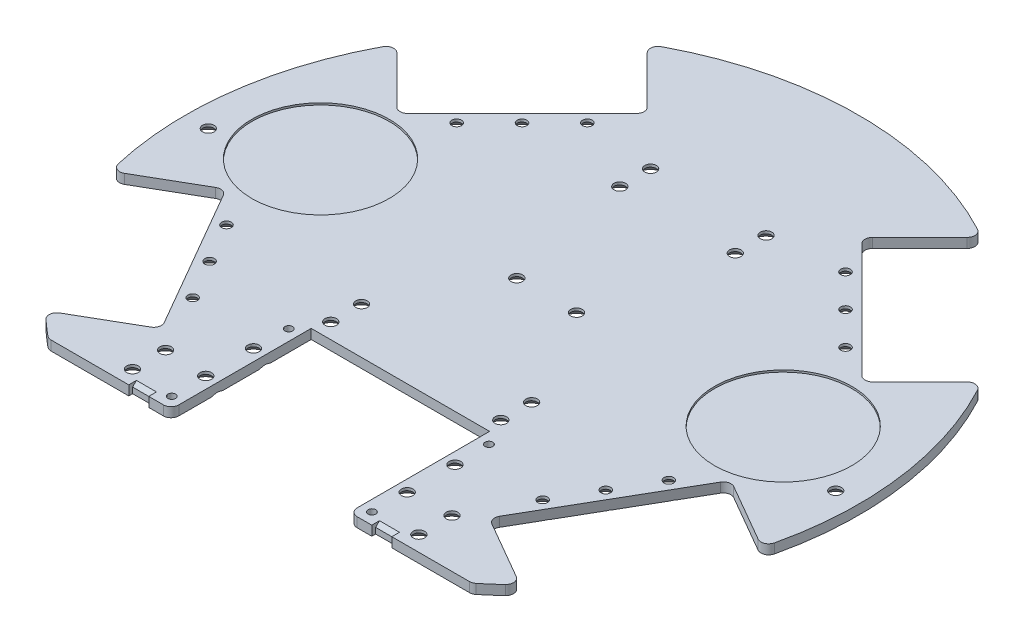
SolidWorks part; units mm, degrees
ref_plane "Plano frontal" through (0, 0, 0) normal (0, 0, 1) x (1, 0, 0)
ref_plane "Plano superior" through (0, 0, 0) normal (0, 1, 0) x (1, 0, 0)
ref_plane "Plano direito" through (0, 0, 0) normal (1, 0, 0) x (0, 0, -1)
sketch "Esboço3" plane through (0, 0, 0) normal (0, 1, 0) x (1, 0, 0)
  line L0 (0, 0) -> (0, 52.1999) construction
  line L1 (-21.17, -31.6) -> (21.17, -31.6)
  line L2 (23.17, -33.6) -> (23.17, -66)
  line L3 (25.17, -68) -> (54.353, -68)
  line L4 (0, 0) -> (75.7772, -43.75) construction
  line L5 (82.3092, -20.9631) -> (67.292, -12.2929)
  line L6 (64.5599, -13.025) -> (43.5599, -49.3981)
  line L7 (44.292, -52.1301) -> (59.3092, -60.8003)
  line L8 (0, 0) -> (61.8718, 61.8718) construction
  line L9 (41.552, 74.0789) -> (29.2905, 61.8174)
  line L10 (29.2905, 58.989) -> (58.989, 29.2905)
  line L11 (61.8174, 29.2905) -> (74.0789, 41.552)
  line L12 (-61.8174, 29.2905) -> (-74.0789, 41.552)
  line L13 (-29.2905, 58.989) -> (-58.989, 29.2905)
  line L14 (-41.552, 74.0789) -> (-29.2905, 61.8174)
  line L15 (-44.292, -52.1301) -> (-59.3092, -60.8003)
  line L16 (-64.5599, -13.025) -> (-43.5599, -49.3981)
  line L17 (-82.3092, -20.9631) -> (-67.292, -12.2929)
  line L18 (-25.17, -68) -> (-54.353, -68)
  line L19 (-23.17, -33.6) -> (-23.17, -66)
  line L20 (0, 0) -> (40.5982, 0) construction
  line L21 (0, 87.5) -> (-87.5, 87.5) construction
  line L22 (-87.5, 87.5) -> (-87.5, 0) construction
  line L23 (-23.17, -33.6) -> (-23.17, -31.6)
  line L24 (-23.17, -31.6) -> (-21.17, -31.6)
  line L25 (23.17, -33.6) -> (23.17, -31.6)
  line L26 (23.17, -31.6) -> (21.17, -31.6)
  arc A0 (55.0659, -68) -> (-55.0659, -68) centre (0, 0) ccw construction
  arc A1 (41.0767, 77.259) -> (-41.0767, 77.259) centre (0, 0) ccw
  arc A2 (77.259, 41.0767) -> (85.2579, -19.6809) centre (0, 0) cw
  arc A3 (59.6731, -63.9951) -> (55.6244, -67.5439) centre (0, 0) cw
  arc A4 (41.552, 74.0789) -> (41.0767, 77.259) centre (40.1378, 75.4931) ccw
  arc A5 (74.0789, 41.552) -> (77.259, 41.0767) centre (75.4931, 40.1378) cw
  arc A6 (82.3092, -20.9631) -> (85.2579, -19.6809) centre (83.3092, -19.2311) ccw
  arc A7 (59.3092, -60.8003) -> (59.6731, -63.9951) centre (58.3092, -62.5323) cw
  arc A8 (54.353, -68) -> (55.6244, -67.5439) centre (54.353, -66) ccw
  arc A9 (23.17, -66) -> (25.17, -68) centre (25.17, -66) ccw
  arc A10 (21.17, -31.6) -> (23.17, -33.6) centre (21.17, -33.6) cw construction
  arc A11 (43.5599, -49.3981) -> (44.292, -52.1301) centre (45.292, -50.3981) ccw
  arc A12 (67.292, -12.2929) -> (64.5599, -13.025) centre (66.292, -14.025) ccw
  arc A13 (29.2905, 61.8174) -> (29.2905, 58.989) centre (30.7047, 60.4032) ccw
  arc A14 (58.989, 29.2905) -> (61.8174, 29.2905) centre (60.4032, 30.7047) ccw
  arc A15 (-58.989, 29.2905) -> (-61.8174, 29.2905) centre (-60.4032, 30.7047) cw
  arc A16 (-29.2905, 61.8174) -> (-29.2905, 58.989) centre (-30.7047, 60.4032) cw
  arc A17 (-67.292, -12.2929) -> (-64.5599, -13.025) centre (-66.292, -14.025) cw
  arc A18 (-43.5599, -49.3981) -> (-44.292, -52.1301) centre (-45.292, -50.3981) cw
  arc A19 (-21.17, -31.6) -> (-23.17, -33.6) centre (-21.17, -33.6) ccw construction
  arc A20 (-23.17, -66) -> (-25.17, -68) centre (-25.17, -66) cw
  arc A21 (-54.353, -68) -> (-55.6244, -67.5439) centre (-54.353, -66) cw
  arc A22 (-59.3092, -60.8003) -> (-59.6731, -63.9951) centre (-58.3092, -62.5323) ccw
  arc A23 (-82.3092, -20.9631) -> (-85.2579, -19.6809) centre (-83.3092, -19.2311) cw
  arc A24 (-74.0789, 41.552) -> (-77.259, 41.0767) centre (-75.4931, 40.1378) ccw
  arc A25 (-41.552, 74.0789) -> (-41.0767, 77.259) centre (-40.1378, 75.4931) cw
  arc A26 (-59.6731, -63.9951) -> (-55.6244, -67.5439) centre (0, 0) ccw
  arc A27 (-77.259, 41.0767) -> (-85.2579, -19.6809) centre (0, 0) ccw
  point P1 (-60.4032, 27.8763)
  point P19 (0, -31.6)
  point P24 (43.4326, 75.9596)
  point P27 (75.9596, 43.4326)
  point P30 (84.6125, -22.2929)
  point P33 (61.6125, -62.1301)
  point P39 (23.17, -68)
  point P42 (23.17, -31.6)
  point P45 (42.5599, -51.1301)
  point P48 (65.5599, -11.2929)
  point P51 (27.8763, 60.4032)
  point P54 (60.4032, 27.8763)
  point P88 (-27.8763, 60.4032)
  point P89 (-65.5599, -11.2929)
  point P90 (-42.5599, -51.1301)
  point P91 (-23.17, -31.6)
  point P92 (-23.17, -68)
  point P93 (-61.6125, -62.1301)
  point P94 (-84.6125, -22.2929)
  point P95 (-75.9596, 43.4326)
  point P96 (-43.4326, 75.9596)
  dimension "D1" = 87.5
  dimension "D13" = 2
  dimension "D2" = 36.4
  dimension "D3" = 23.17
  dimension "D4" = 155.5
  dimension "D5" = 30
  dimension "D6" = 46
  dimension "D7" = 23
  dimension "D8" = 22
  dimension "D9" = 45
  dimension "D10" = 46
  dimension "D11" = 22
  dimension "D12" = 23
extrude "Ressalto-extrusão1" add sketch "Esboço3" along normal blind 2.5
sketch "Esboço7" plane through (0, 2.5, 0) normal (0, 1, 0) x (1, 0, 0)
  line L0 (28.97, -68) -> (28.97, -62)
  line L1 (25.17, -68) -> (54.353, -68) construction
  line L2 (28.97, -62) -> (34.17, -62)
  line L3 (34.17, -62) -> (34.17, -68)
  line L4 (34.17, -68) -> (28.97, -68)
  line L5 (23.17, -31.6) -> (23.17, -66) construction
  line L6 (34.17, -67) -> (28.97, -67)
  line L7 (-28.97, -68) -> (-28.97, -62)
  line L8 (-54.353, -68) -> (-25.17, -68) construction
  line L9 (-28.97, -62) -> (-34.17, -62)
  line L10 (-34.17, -62) -> (-34.17, -68)
  line L11 (-34.17, -68) -> (-28.97, -68)
  line L12 (-28.97, -67) -> (-34.17, -67)
  line L13 (-23.17, -66) -> (-23.17, -31.6) construction
  line M20 (-54.353, -68) -> (-25.17, -68)
  line M28 (25.17, -68) -> (54.353, -68)
  dimension "D1" = 5.8
  dimension "D2" = 5.2
  dimension "D3" = 6
  dimension "D4" = 1
  dimension "D5" = 6
  dimension "D6" = 5.2
  dimension "D7" = 1
  dimension "D8" = 5.8
extrude "Corte-extrusão1" cut sketch "Esboço7" against normal up to next contours L3 L6 L0 M28 | L7 L12 L10 M20 region at (31.57, 2.5, 67.5) region at (-31.57, 2.5, 67.5)
sketch "Esboço9" plane through (0, 2.5, 0) normal (0, 1, 0) x (1, 0, 0)
  line L0 (-19, -31.6) -> (-19, 1.4)
  line L1 (-23.17, -31.6) -> (23.17, -31.6) construction
  line L2 (-17, 3.4) -> (17, 3.4)
  line L3 (19, 1.4) -> (19, -31.6)
  line L4 (-23.17, -31.6) -> (23.17, -31.6) construction
  line L5 (0, -31.6) -> (0, 3.4) construction
  line L6 (-19, -31.6) -> (19, -31.6)
  arc A0 (17, 3.4) -> (19, 1.4) centre (17, 1.4) cw
  arc A1 (-19, 1.4) -> (-17, 3.4) centre (-17, 1.4) cw
  point P11 (19, 3.4)
  point P14 (-19, 3.4)
  dimension "D3" = 2
  dimension "D1" = 35
  dimension "D2" = 38
chamfer "Chanfro1" distance 1 angle 45 2 edges at (-31.57, 2.5, 67) (31.57, 2.5, 67)
sketch "Esboço10" plane through (0, 2.5, 0) normal (0, 1, 0) x (1, 0, 0)
  line L0 (-81.5, 0) -> (81.5, 0) construction
  circle A0 centre (37.2, -64) radius 1.25 construction
  circle A1 centre (37.2, -55.4) radius 1.25 construction
  circle A2 centre (57.4619, -19.3192) radius 1.25 construction
  circle A3 centre (51.4619, -29.7115) radius 1.25 construction
  circle A4 centre (45.4619, -40.1038) radius 1.25 construction
  circle A5 centre (81.5, 0) radius 1.25 construction
  circle A6 centre (50.5037, 33.5332) radius 1.25 construction
  circle A7 centre (42.0184, 42.0184) radius 1.25 construction
  circle A8 centre (33.5332, 50.5037) radius 1.25 construction
  circle A9 centre (-33.5332, 50.5037) radius 1.25 construction
  circle A10 centre (-42.0184, 42.0184) radius 1.25 construction
  circle A11 centre (-50.5037, 33.5332) radius 1.25 construction
  circle A12 centre (-81.5, 0) radius 1.25 construction
  circle A13 centre (-57.4619, -19.3192) radius 1.25 construction
  circle A14 centre (-51.4619, -29.7115) radius 1.25 construction
  circle A15 centre (-45.4619, -40.1038) radius 1.25 construction
  circle A16 centre (-37.2, -64) radius 1.25 construction
  circle A17 centre (-37.2, -55.4) radius 1.25 construction
  circle A19 centre (-26.17, -56) radius 1.25 construction
  circle A20 centre (-26.17, -43.6) radius 1.25 construction
  circle A23 centre (26.17, -56) radius 1.25 construction
  circle A24 centre (26.17, -43.6) radius 1.25 construction
  circle A26 centre (22.09, -19.6) radius 1.25 construction
  circle A27 centre (22.09, -27.6) radius 1.25 construction
  circle A28 centre (-22.09, -27.6) radius 1.25 construction
  circle A29 centre (-22.09, -19.6) radius 1.25 construction
  circle A30 centre (-15, 40.4) radius 1.25 construction
  circle A31 centre (-15, 48.4) radius 1.25 construction
  circle A32 centre (15, 48.4) radius 1.25 construction
  circle A33 centre (15, 40.4) radius 1.25 construction
  circle A34 centre (37.2, -64) radius 1.25 construction
  circle A35 centre (37.2, -55.4) radius 1.25 construction
  circle A36 centre (57.4619, -19.3192) radius 1.25 construction
  circle A37 centre (51.4619, -29.7115) radius 1.25 construction
  circle A38 centre (45.4619, -40.1038) radius 1.25 construction
  circle A39 centre (81.5, 0) radius 1.25 construction
  circle A40 centre (50.5037, 33.5332) radius 1.25 construction
  circle A41 centre (42.0184, 42.0184) radius 1.25 construction
  circle A42 centre (33.5332, 50.5037) radius 1.25 construction
  circle A43 centre (-33.5332, 50.5037) radius 1.25 construction
  circle A44 centre (-42.0184, 42.0184) radius 1.25 construction
  circle A45 centre (-50.5037, 33.5332) radius 1.25 construction
  circle A46 centre (-81.5, 0) radius 1.25 construction
  circle A47 centre (-57.4619, -19.3192) radius 1.25 construction
  circle A48 centre (-51.4619, -29.7115) radius 1.25 construction
  circle A49 centre (-45.4619, -40.1038) radius 1.25 construction
  circle A50 centre (-37.2, -64) radius 1.25 construction
  circle A51 centre (-37.2, -55.4) radius 1.25 construction
  circle A52 centre (-26, -65) radius 1 construction
  circle A53 centre (-26.17, -56) radius 1.25 construction
  circle A54 centre (-26.17, -43.6) radius 1.25 construction
  circle A55 centre (26, -34.6) radius 1 construction
  circle A56 centre (-26, -65) radius 1
  circle A57 centre (26.17, -56) radius 1.25 construction
  circle A58 centre (26.17, -43.6) radius 1.25 construction
  circle A59 centre (26, -34.6) radius 1
  circle A60 centre (22.09, -19.6) radius 1.25 construction
  circle A61 centre (22.09, -27.6) radius 1.25 construction
  circle A62 centre (-22.09, -27.6) radius 1.25 construction
  circle A63 centre (-22.09, -19.6) radius 1.25 construction
  circle A64 centre (-15, 40.4) radius 1.25 construction
  circle A65 centre (-15, 48.4) radius 1.25 construction
  circle A66 centre (15, 48.4) radius 1.25 construction
  circle A67 centre (15, 40.4) radius 1.25 construction
  circle A68 centre (-7.75, 6.4) radius 1.25 construction
  circle A69 centre (7.75, 6.4) radius 1.25 construction
  circle A70 centre (-7.75, 6.4) radius 1.25 construction
  circle A71 centre (7.75, 6.4) radius 1.25 construction
  circle A72 centre (-45.4619, -40.1038) radius 1.25
  circle A73 centre (-51.4619, -29.7115) radius 1.25
  circle A74 centre (-57.4619, -19.3192) radius 1.25
  circle A75 centre (81.5, 0) radius 1.5
  circle A76 centre (-50.5037, 33.5332) radius 1.25
  circle A77 centre (-42.0184, 42.0184) radius 1.25
  circle A78 centre (-33.5332, 50.5037) radius 1.25
  circle A79 centre (37.2, -55.4) radius 1.5
  circle A80 centre (37.2, -64) radius 1.5
  circle A81 centre (26, -65) radius 1.5 construction
  circle A82 centre (26.17, -56) radius 1.5
  circle A83 centre (26.17, -43.6) radius 1.5
  circle A84 centre (26, -34.6) radius 1.5 construction
  circle A85 centre (22.09, -27.6) radius 1.5
  circle A86 centre (22.09, -19.6) radius 1.5
  circle A87 centre (-22.09, -19.6) radius 1.5
  circle A88 centre (-22.09, -27.6) radius 1.5
  circle A89 centre (-26, -34.6) radius 1.5 construction
  circle A90 centre (-26.17, -43.6) radius 1.5
  circle A91 centre (-26.17, -56) radius 1.5
  circle A92 centre (-26, -65) radius 1.5 construction
  circle A93 centre (-37.2, -64) radius 1.5
  circle A94 centre (-37.2, -55.4) radius 1.5
  circle A95 centre (33.5332, 50.5037) radius 1.25
  circle A96 centre (42.0184, 42.0184) radius 1.25
  circle A97 centre (50.5037, 33.5332) radius 1.25
  circle A98 centre (-81.5, 0) radius 1.5
  circle A99 centre (45.4619, -40.1038) radius 1.25
  circle A100 centre (51.4619, -29.7115) radius 1.25
  circle A101 centre (57.4619, -19.3192) radius 1.25
  circle A102 centre (-15, 48.4) radius 1.5
  circle A103 centre (-15, 40.4) radius 1.5
  circle A104 centre (15, 48.4) radius 1.5
  circle A105 centre (15, 40.4) radius 1.5
  circle A106 centre (-7.75, 6.4) radius 1.5
  circle A107 centre (7.75, 6.4) radius 1.5
  circle A108 centre (26, -65) radius 1 construction
  circle A109 centre (26, -65) radius 1
  circle A110 centre (-26, -34.6) radius 1 construction
  circle A111 centre (-26, -34.6) radius 1
  dimension "D1" = 3
extrude "Corte-extrusão4" cut sketch "Esboço10" against normal up to next (2.5 mm away)
chamfer "Chanfro2" distance 1.8 angle 45 32 edges at (81.5, 0, 1.5) (15, 0, -46.9) (15, 0, -38.9) (-15, 0, -38.9) (-15, 0, -46.9) (-7.75, 0, -4.9) (7.75, 0, -4.9) (22.09, 0, 21.1) (22.09, 0, 29.1) (26.17, 0, 45.1) (26.17, 0, 57.5) (37.2, 0, 56.9) (37.2, 0, 65.5) (-22.09, 0, 21.1) (-22.09, 0, 29.1) (-26.17, 0, 45.1) (-26.17, 0, 57.5) (-37.2, 0, 65.5) (-37.2, 0, 56.9) (-81.5, 0, 1.5) (-45.4619, 0, 41.3538) (-51.4619, 0, 30.9615) (-57.4619, 0, 20.5692) (-33.5332, 0, -49.2537) (-42.0184, 0, -40.7684) (-50.5037, 0, -32.2832) (33.5332, 0, -49.2537) (42.0184, 0, -40.7684) (50.5037, 0, -32.2832) (57.4619, 0, 20.5692) (51.4619, 0, 30.9615) (45.4619, 0, 41.3538)
sketch "Esboço11" plane through (0, 2.5, 0) normal (0, 1, 0) x (1, 0, 0)
  circle A0 centre (-60.0965, 7.7513) radius 17.85 construction
  circle A1 centre (60.0965, 7.7513) radius 17.85 construction
  circle A2 centre (-60.0965, 7.7513) radius 17.85
  circle A3 centre (60.0965, 7.7513) radius 17.85
extrude "Corte-extrusão5" cut sketch "Esboço11" against normal blind 0.5
